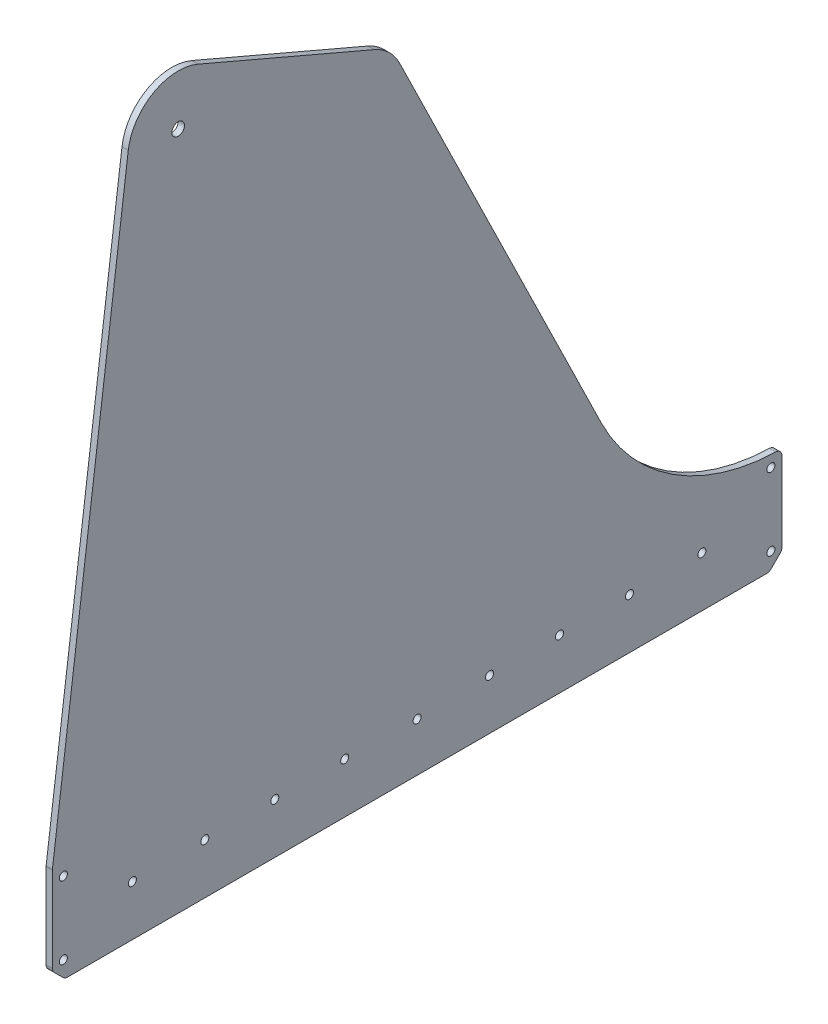
SolidWorks part; units mm, degrees
ref_plane "Front Plane" through (0, 0, 0) normal (0, 0, 1) x (1, 0, 0)
ref_plane "Top Plane" through (0, 0, 0) normal (0, 1, 0) x (1, 0, 0)
ref_plane "Right Plane" through (0, 0, 0) normal (1, 0, 0) x (0, 0, -1)
sketch "Sketch2" plane through (0, 0, 0) normal (1, 0, 0) x (0, 0, -1)
  line L0 (0, 0) -> (0, 50.8)
  line L1 (0, 50.8) -> (38.311, 346.1672)
  line L4 (368.3, 50.8) -> (368.3, 0)
  line L5 (368.3, 0) -> (0, 0)
  line L6 (73.5056, 366.2463) -> (162.4056, 328.1463)
  line L7 (175.2177, 315.9585) -> (277.0291, 107.7662)
  line L8 (368.3, 50.8) -> (419.4553, 50.8) construction
  line L9 (0, 374.65) -> (368.3, 374.65) construction
  arc A0 (38.311, 346.1672) -> (73.5056, 366.2463) centre (63.5, 342.9) cw
  arc A1 (162.4056, 328.1463) -> (175.2177, 315.9585) centre (152.4, 304.8) cw
  arc A2 (277.0291, 107.7662) -> (368.3, 50.8) centre (368.3, 152.4) ccw
  dimension "D6" = 25.4
  dimension "D3" = 101.6
  dimension "D7" = 25.4
  dimension "D1" = 368.3
  dimension "D2" = 50.8
  dimension "D4" = 304.8
  dimension "D5" = 342.9
  dimension "D8" = 374.65
  dimension "D9" = 304.8
  dimension "D10" = 152.4
extrude "Plate" add sketch "Sketch2" along normal blind 3.175
sketch "Sketch4" plane through (3.175, 0, 0) normal (1, 0, 0) x (0, 0, -1)
  line L4 (184.15, 24.6062) -> (220.7174, 25.4) construction
  line L7 (220.7174, 25.4) -> (256.0234, 25.4) construction
  line L8 (256.0234, 25.4) -> (291.3294, 25.4) construction
  line L9 (291.3294, 25.4) -> (327.9054, 25.4) construction
  line L12 (184.15, 24.6062) -> (147.5826, 25.4) construction
  line L13 (147.5826, 25.4) -> (112.2766, 25.4) construction
  line L14 (112.2766, 25.4) -> (76.9706, 25.4) construction
  line L15 (76.9706, 25.4) -> (40.3946, 25.4) construction
  line L18 (0, 0) -> (368.3, 0) construction
  line L19 (368.3, 0) -> (368.3, 50.8) construction
  point P0 (184.15, 24.6062)
  point P10 (220.7174, 25.4)
  point P12 (256.0234, 25.4)
  point P14 (291.3294, 25.4)
  point P16 (327.9054, 25.4)
  point P18 (147.5826, 25.4)
  point P20 (112.2766, 25.4)
  point P22 (76.9706, 25.4)
  point P24 (40.3946, 25.4)
  point P50 (184.15, 0)
  point P54 (368.3, 25.4)
  dimension "Small-Large Gear Spacing" = 36.576
  dimension "Small to Small Hole Spacing" = 35.306
  dimension "D1" = 287.5108
  dimension "D2" = 0.7937
hole_wizard "Drive Holes" positions "Sketch4" profile "Sketch6" hole size "#8" standard "ANSI Inch" end condition through all
sketch "Sketch6" plane through (3.175, 24.6062, -184.15) normal (0, 1, 0) x (0, 0, -1)
  line L0 (0, 0) -> (0, 3.175)
  line L1 (0, 3.175) -> (2.032, 3.175)
  line L2 (2.032, 3.175) -> (2.032, 0)
  line L5 (2.032, 0) -> (0, 0)
  line L11 (0, -6.35) -> (0, 107.95) construction
  dimension "Thru Hole Dia." = 4.064
  dimension "Thru Hole Depth" = 3.175
sketch "Sketch3" plane through (3.175, 0, 0) normal (1, 0, 0) x (0, 0, -1)
  circle A0 centre (63.5, 342.9) radius 3.175
  dimension "D1" = 6.35
extrude "Tube Pivot Holes" cut sketch "Sketch3" against normal through all
chamfer "Bottom Corner Chamfer" distance 6.35 angle 45 2 edges at (1.5875, 0, -368.3) (1.5875, 0, 0)
fillet "Bottom Corner Fillet" radius 3.175 6 edges at (1.5875, 50.8, 0) (1.5875, 0, -6.35) (1.5875, 6.35, 0) (1.5875, 0, -361.95) (1.5875, 6.35, -368.3) (1.5875, 50.8, -368.3)
sketch "Sketch7" plane through (3.175, 0, 0) normal (1, 0, 0) x (0, 0, -1)
  point P0 (5.5562, 45.2438)
  point P1 (5.5562, 8.6515)
  point P3 (362.7438, 45.2438)
  point P5 (362.7438, 8.6515)
hole_wizard "Carbon Cap Holes" positions "Sketch7" profile "Sketch8" hole size "#8" standard "ANSI Inch" end condition through all
sketch "Sketch8" plane through (3.175, 45.2438, -5.5562) normal (0, 1, 0) x (0, 0, -1)
  line L0 (0, 0) -> (0, 3.175)
  line L1 (0, 3.175) -> (2.032, 3.175)
  line L2 (2.032, 3.175) -> (2.032, 0)
  line L5 (2.032, 0) -> (0, 0)
  line L11 (0, -6.35) -> (0, 107.95) construction
  dimension "Thru Hole Dia." = 4.064
  dimension "Thru Hole Depth" = 3.175
equation "\"Small to Small Gear Spacing\" = ( 28 / 20 ) - .01"
equation "\"Small to Big Gear Spacing\"= ( 28 / 40 ) + ( 30 / 40 ) - .01"
equation "\"Small-Large Gear Spacing@Sketch4\"= \"Small to Big Gear Spacing\""
equation "\"Small to Small Hole Spacing@Sketch4\"= \"Small to Small Gear Spacing\""
